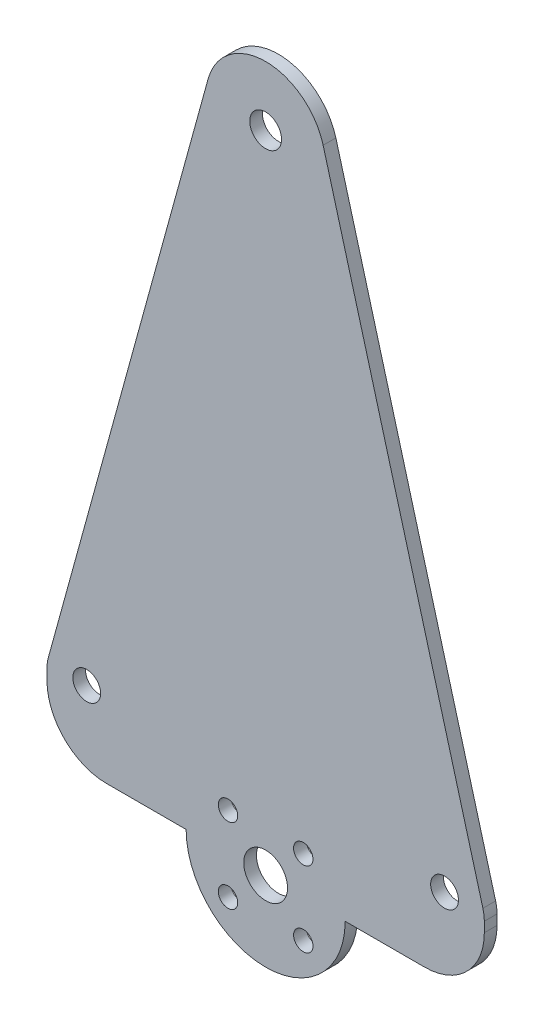
SolidWorks part; units mm, degrees
material "Acrylic (Medium-high impact)"
ref_plane "Front Plane" through (0, 0, 0) normal (0, 0, 1) x (1, 0, 0)
ref_plane "Top Plane" through (0, 0, 0) normal (0, 1, 0) x (1, 0, 0)
ref_plane "Right Plane" through (0, 0, 0) normal (1, 0, 0) x (0, 0, -1)
sketch "Sketch1" plane through (0, 0, 0) normal (0, 0, 1) x (1, 0, 0)
  line L0 (0, 0) -> (57.15, 0) construction
  line L1 (41.275, -11.9697) -> (53.975, -11.9697)
  line L2 (19.3909, 93.6034) -> (-6.1227, 0.8265)
  line L3 (63.5, -0.8572) -> (63.5, -2.4447)
  line L4 (15.875, -11.9697) -> (3.175, -11.9697)
  line L5 (-6.35, -2.4447) -> (-6.35, -0.8572)
  line L6 (63.2727, 0.8265) -> (37.7591, 93.6034)
  line L7 (28.575, 100.6028) -> (28.575, 0) construction
  line L8 (28.575, -11.9697) -> (34.5854, -17.9801) construction
  line L9 (28.575, -11.9697) -> (22.5646, -5.9593) construction
  line L10 (28.575, -11.9697) -> (22.5646, -17.9801) construction
  line L11 (28.575, -11.9697) -> (34.5854, -5.9593) construction
  circle A0 centre (0, 0) radius 2.2225
  circle A1 centre (57.15, 0) radius 2.2225
  arc A2 (-6.35, -0.8572) -> (-6.1227, 0.8265) centre (0, -0.8572) cw
  circle A3 centre (22.5646, -5.9593) radius 1.55
  arc A4 (53.975, -11.9697) -> (63.5, -2.4447) centre (53.975, -2.4447) ccw
  arc A5 (63.5, -0.8572) -> (63.2727, 0.8265) centre (57.15, -0.8572) ccw
  arc A6 (37.7591, 93.6034) -> (19.3909, 93.6034) centre (28.575, 91.0778) ccw
  circle A7 centre (28.575, 91.0778) radius 2.54
  arc A8 (15.875, -11.9697) -> (41.275, -11.9697) centre (28.575, -11.9697) ccw
  circle A9 centre (28.575, -11.9697) radius 3.5
  circle A10 centre (34.5854, -17.9801) radius 1.55
  arc A11 (-6.35, -2.4447) -> (3.175, -11.9697) centre (3.175, -2.4447) ccw
  circle A12 centre (34.5854, -5.9593) radius 1.55
  circle A13 centre (22.5646, -17.9801) radius 1.55
  point P17 (28.575, -11.9697)
  point P18 (-6.35, -11.9697)
  dimension "D1" = 4.445
  dimension "D2" = 4.445
  dimension "D6" = 6.35
  dimension "D7" = 9.525
  dimension "D9" = 9.525
  dimension "D8" = 5.08
  dimension "D10" = 12.7
  dimension "D11" = 7
  dimension "D13" = 3.1
  dimension "D5" = 9.525
  dimension "D15" = 3.1
  dimension "D16" = 3.1
  dimension "D17" = 3.1
  dimension "D3" = 57.15
  dimension "D4" = 11.1125
  dimension "D12" = 8.5
  dimension "D14" = 8.5
extrude "Boss-Extrude1" add sketch "Sketch1" along normal blind 2.032
